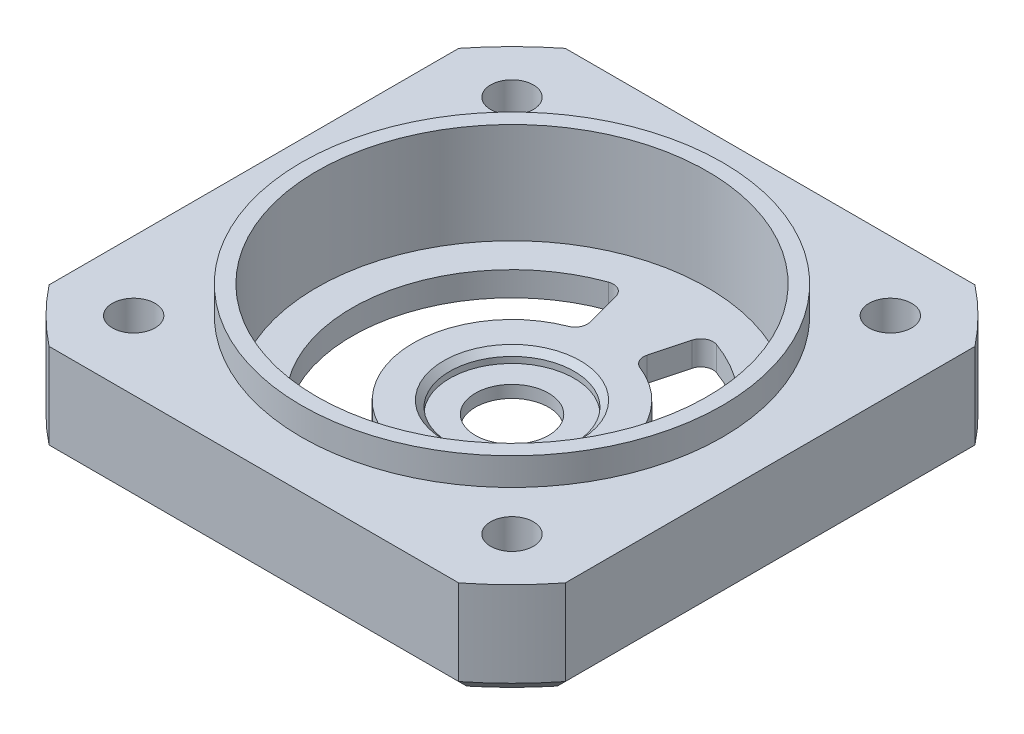
SolidWorks part; units mm, degrees
ref_plane "Front Plane" through (0, 0, 0) normal (0, 0, 1) x (1, 0, 0)
ref_plane "Top Plane" through (0, 0, 0) normal (0, 1, 0) x (1, 0, 0)
ref_plane "Right Plane" through (0, 0, 0) normal (1, 0, 0) x (0, 0, -1)
sketch "Sketch2" plane through (0, 0, 0) normal (0, 1, 0) x (1, 0, 0)
  line L1 (-21.15, 21.15) -> (21.15, 21.15)
  line L2 (-21.15, 21.15) -> (-21.15, -21.15)
  line L3 (-21.15, -21.15) -> (21.15, -21.15)
  line L4 (21.15, 21.15) -> (21.15, -21.15)
  line L5 (-21.15, 21.15) -> (21.15, -21.15) construction
  line L6 (-21.15, -21.15) -> (21.15, 21.15) construction
  point P0 (0, 0)
  dimension "D1" = 42.3
extrude "Boss-Extrude1" add sketch "Sketch2" along normal blind 8
sketch "Sketch5" plane through (0, 8, 0) normal (0, 1, 0) x (1, 0, 0)
  circle A0 centre (0, 0) radius 27
  circle A1 centre (0, 0) radius 29.9106
  dimension "D1" = 54
extrude "Cut-Extrude4" cut sketch "Sketch5" against normal through all
sketch "Sketch6" plane through (0, 8, 0) normal (0, 1, 0) x (1, 0, 0)
  circle A2 centre (0, 0) radius 16
  circle A3 centre (0, 0) radius 10 construction
  dimension "D1" = 32
  dimension "D5" = 20
extrude "Cut-Extrude7" cut sketch "Sketch6" against normal offset from surface (7 mm away) 1 up to face at (0, 0, 0)
sketch "Sketch8" plane through (0, 1, 0) normal (0, 1, 0) x (1, 0, 0)
  circle A0 centre (0, 0) radius 5.1
  circle A2 centre (0, 0) radius 16
  circle A3 centre (0, 0) radius 16
  dimension "D1" = 10.2
  dimension "D2" = 0
extrude "Boss-Extrude3" add sketch "Sketch8" along normal blind 1
sketch "Sketch9" plane through (0, 2, 0) normal (0, 1, 0) x (1, 0, 0)
  line L0 (3.3905, 12.6536) -> (2.0964, 7.824)
  line L1 (3.3905, -12.6536) -> (2.0964, -7.824)
  line L2 (2.0964, -7.824) -> (0, 0) construction
  line L3 (2.0964, 7.824) -> (0, 0) construction
  line L4 (-21.15, 16.7833) -> (-21.15, -16.7833) construction
  line L5 (0, -4.4) -> (0, 4.4) construction
  line L6 (-2.0964, 7.824) -> (0, 0) construction
  line L7 (-2.0964, -7.824) -> (0, 0) construction
  line L8 (-3.3905, -12.6536) -> (-2.0964, -7.824)
  line L9 (-3.3905, 12.6536) -> (-2.0964, 7.824)
  arc A0 (3.3905, 12.6536) -> (3.3905, -12.6536) centre (0, 0) cw
  circle A1 centre (0, 0) radius 5.1 construction
  arc A2 (2.0964, 7.824) -> (2.0964, -7.824) centre (0, 0) cw
  arc A3 (-2.0964, 7.824) -> (-2.0964, -7.824) centre (0, 0) ccw
  arc A4 (-3.3905, 12.6536) -> (-3.3905, -12.6536) centre (0, 0) ccw
  dimension "D1" = 15
  dimension "D4" = 3
  dimension "D2" = 15
  dimension "D3" = 5
extrude "Cut-Extrude8" cut sketch "Sketch9" against normal through all
fillet "Fillet1" radius 1 8 edges at (-3.3905, 1, 12.6536) (-2.0964, 1, -7.824) (-2.0964, 1, 7.824) (-3.3905, 1, -12.6536) (2.0964, 1, 7.824) (2.0964, 1, -7.824) (3.3905, 1, 12.6536) (3.3905, 1, -12.6536)
sketch "Sketch10" plane through (0, 1, 0) normal (0, 1, 0) x (1, 0, 0)
  circle A0 centre (0, 0) radius 3
  dimension "D1" = 6
extrude "Cut-Extrude9" cut sketch "Sketch10" against normal through all
sketch "Sketch7" plane through (0, 8, 0) normal (0, 1, 0) x (1, 0, 0)
  line L1 (-15.5, 15.5) -> (15.5, 15.5) construction
  line L2 (-15.5, 15.5) -> (-15.5, -15.5) construction
  line L3 (-15.5, -15.5) -> (15.5, -15.5) construction
  line L4 (15.5, 15.5) -> (15.5, -15.5) construction
  line L5 (-15.5, 15.5) -> (15.5, -15.5) construction
  line L6 (-15.5, -15.5) -> (15.5, 15.5) construction
  circle A0 centre (-15.5, 15.5) radius 1.75
  circle A1 centre (15.5, 15.5) radius 1.75
  circle A2 centre (15.5, -15.5) radius 1.75
  circle A3 centre (-15.5, -15.5) radius 1.75
  point P0 (0, 0)
  point P16 (0, 0)
  dimension "D3" = 3.5
  dimension "D1" = 31
  dimension "D2" = 31
  dimension "D4" = 4
extrude "Cut-Extrude6" cut sketch "Sketch7" against normal through all
chamfer "Chamfer4" distance 1 angle 45 8 edges at (19.0919, 0, 19.0919) (0, 0, 21.15) (-19.0919, 0, 19.0919) (-21.15, 0, 0) (-19.0919, 0, -19.0919) (0, 0, -21.15) (19.0919, 0, -19.0919) (21.15, 0, 0)
chamfer "Chamfer5" distance 2 angle 45 4 edges at (-15.5, 0, -13.75) (15.5, 0, -13.75) (15.5, 0, 17.25) (-15.5, 0, 17.25)
chamfer "Chamfer6" distance 0.5 angle 45 1 edges at (0, 2, 5.1)
sketch "Sketch11" plane through (0, 8, 0) normal (0, 1, 0) x (1, 0, 0)
  circle A0 centre (0, 0) radius 17.25
  circle A1 centre (0, 0) radius 16 construction
  circle A2 centre (0, 0) radius 16
  dimension "D1" = 1.25
extrude "Boss-Extrude4" add sketch "Sketch11" along normal blind 2.25
